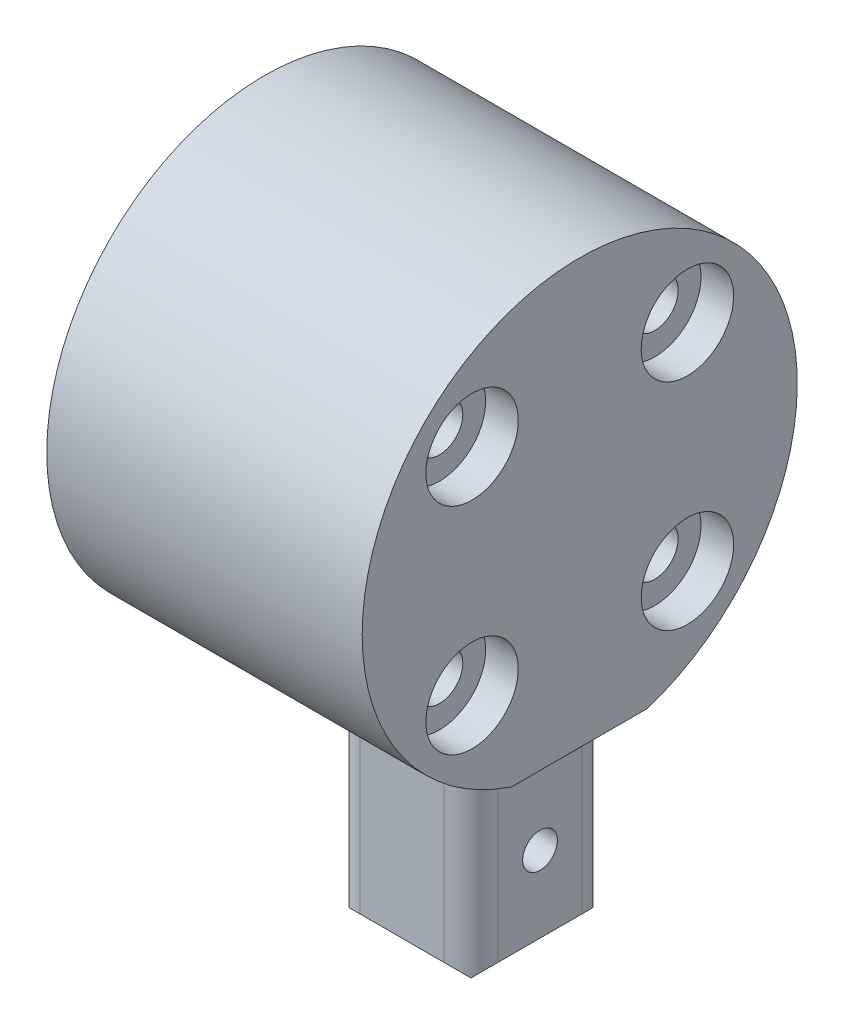
SolidWorks part; units mm, degrees
ref_plane "前视基准面" through (0, 0, 0) normal (0, 0, 1) x (1, 0, 0)
ref_plane "上视基准面" through (0, 0, 0) normal (0, 1, 0) x (1, 0, 0)
ref_plane "右视基准面" through (0, 0, 0) normal (1, 0, 0) x (0, 0, -1)
sketch "草图1" plane through (0, 0, 0) normal (1, 0, 0) x (0, 0, -1)
  circle A0 centre (0, 0) radius 20
  dimension "D1" = 40
extrude "凸台-拉伸1" add sketch "草图1" along normal blind 10
sketch "草图2" plane through (0, 0, 0) normal (-1, 0, 0) x (0, 0, 1)
  line L1 (-7.5, -15.25) -> (7.5, -15.25)
  line L2 (-7.5, -15.25) -> (-7.5, 15.25)
  line L3 (-7.5, 15.25) -> (7.5, 15.25)
  line L4 (7.5, -15.25) -> (7.5, 15.25)
  line L5 (-7.5, -15.25) -> (7.5, 15.25) construction
  line L6 (-7.5, 15.25) -> (7.5, -15.25) construction
  point P0 (0, 0)
  dimension "D1" = 15
  dimension "D2" = 30.5
extrude "切除-拉伸1" cut sketch "草图2" against normal blind 4
sketch "草图3" plane through (4, 0, 0) normal (-1, 0, 0) x (0, 0, 1)
  circle A0 centre (0, 0) radius 8.75
  dimension "D1" = 17.5
extrude "切除-拉伸2" cut sketch "草图3" along normal blind 4
sketch "草图4" plane through (0, 0, 0) normal (-1, 0, 0) x (0, 0, 1)
  line L1 (-9, -16) -> (9, -16)
  line L2 (-9, -16) -> (-9, 16)
  line L3 (-9, 16) -> (9, 16)
  line L4 (9, -16) -> (9, 16)
  line L5 (-9, -16) -> (9, 16) construction
  line L6 (-9, 16) -> (9, -16) construction
  circle A0 centre (0, 0) radius 20
  dimension "D3" = 40
  dimension "D1" = 32
  dimension "D2" = 18
extrude "凸台-拉伸2" add sketch "草图4" along normal blind 19
fillet "圆角1" radius 3 4 edges at (-9.5, -16, -9) (-9.5, -16, 9) (-9.5, 16, -9) (-9.5, 16, 9)
sketch "草图5" plane through (-19, 0, 0) normal (-1, 0, 0) x (0, 0, 1)
  line L0 (-6, -16) -> (6, -16) construction
  line L1 (6, 16) -> (-6, 16) construction
  circle A0 centre (0, -16) radius 2.5
  circle A1 centre (0, 16) radius 2.5
  dimension "D1" = 5
  dimension "D2" = 5
extrude "切除-拉伸3" cut sketch "草图5" against normal blind 20
fillet "圆角2" radius 3 4 edges at (-9.5, -16, -2.5) (-9.5, -16, 2.5) (-9.5, 16, -2.5) (-9.5, 16, 2.5)
sketch "草图6" plane through (10, 0, 0) normal (1, 0, 0) x (0, 0, -1)
  line L0 (0, 0) -> (20, 0) construction
  line L1 (0, 0) -> (18.216, -18.216) construction
  circle A0 centre (0, 0) radius 14 construction
  circle A2 centre (9.8995, -9.8995) radius 2.15
  circle A3 centre (0, 0) radius 14 construction
  circle A4 centre (-9.8995, -9.8995) radius 2.15
  circle A5 centre (0, 0) radius 14 construction
  circle A6 centre (-9.8995, 9.8995) radius 2.15
  circle A7 centre (0, 0) radius 14 construction
  circle A8 centre (9.8995, 9.8995) radius 2.15
  point P21 (0, 0)
  dimension "D1" = 28
  dimension "D3" = 4.3
  dimension "D2" = 45
  dimension "D4" = 4
extrude "切除-拉伸4" cut sketch "草图6" against normal blind 43
fillet "圆角3" radius 1 8 edges at (-9.5, -11.8523, 9) (-9.5, -7.9467, 9) (-9.5, -11.8523, -9) (-9.5, -7.9467, -9) (-9.5, 7.9467, -9) (-9.5, 11.8523, -9) (-9.5, 7.9467, 9) (-9.5, 11.8523, 9)
sketch "草图7" plane through (10, 0, 0) normal (1, 0, 0) x (0, 0, -1)
  circle A0 centre (9.8995, -9.8995) radius 4.25
  dimension "D1" = 8.5
extrude "切除-拉伸5" cut sketch "草图7" against normal blind 3
pattern_circular "阵列(圆周)1" count 4 over 360 about axis through (10, 0, 0) along (1, 0, 0) of "切除-拉伸5"
sketch "草图8" plane through (10, 0, 0) normal (1, 0, 0) x (0, 0, -1)
  line L1 (-11.4701, -19) -> (11.4701, -19)
  line L2 (-11.4701, -19) -> (-11.4701, -28.3124)
  line L3 (-11.4701, -28.3124) -> (11.4701, -28.3124)
  line L4 (11.4701, -19) -> (11.4701, -28.3124)
  line L5 (-11.4701, -19) -> (11.4701, -28.3124) construction
  line L6 (-11.4701, -28.3124) -> (11.4701, -19) construction
  point P0 (0, -23.6562)
  dimension "D1" = 19
extrude "切除-拉伸6" cut sketch "草图8" against normal blind 20
sketch "草图9" plane through (0, -19, 0) normal (0, -1, 0) x (1, 0, 0)
  line L1 (-3, -3) -> (3, -3)
  line L2 (-3, -3) -> (-3, 3)
  line L3 (-3, 3) -> (3, 3)
  line L4 (3, -3) -> (3, 3)
  line L5 (-3, -3) -> (3, 3) construction
  line L6 (-3, 3) -> (3, -3) construction
  point P0 (0, 0)
  dimension "D1" = 6
  dimension "D2" = 6
extrude "切除-拉伸7" cut sketch "草图9" against normal blind 4
sketch "草图10" plane through (0, -19, 0) normal (0, -1, 0) x (1, 0, 0)
  line L0 (10, -6.245) -> (10, 6.245) construction
  line L1 (-6.35, -6.35) -> (6.35, -6.35)
  line L2 (-6.35, -6.35) -> (-6.35, 6.35)
  line L3 (-6.35, 6.35) -> (6.35, 6.35)
  line L4 (6.35, -6.35) -> (6.35, 6.35)
  line L5 (-6.35, -6.35) -> (6.35, 6.35) construction
  line L6 (-6.35, 6.35) -> (6.35, -6.35) construction
  line L7 (-3, -3) -> (3, -3)
  line L8 (-3, -3) -> (-3, 3)
  line L9 (-3, 3) -> (3, 3)
  line L10 (3, -3) -> (3, 3)
  line L11 (-3, -3) -> (3, 3) construction
  line L12 (-3, 3) -> (3, -3) construction
  point P0 (0, 0)
  point P6 (0, 0)
  dimension "D1" = 12.7
  dimension "D2" = 12.7
  dimension "D3" = 10
extrude "凸台-拉伸3" add sketch "草图10" along normal blind 20 and the other way blind 0.5
sketch "草图11" plane through (-6.35, 0, 0) normal (-1, 0, 0) x (0, 0, 1)
  line L0 (-6.245, -19) -> (6.245, -19) construction
  line L1 (6.35, -18.9652) -> (6.35, -39) construction
  line L2 (-6.35, -18.9652) -> (-6.35, -39) construction
  circle A0 centre (0, -29) radius 1.6
  dimension "D1" = 3.2
  dimension "D2" = 10
  dimension "D3" = 6.35
  dimension "D4" = 6.35
extrude "切除-拉伸8" cut sketch "草图11" against normal blind 20
chamfer "倒角1" distance 3 angle 45 2 edges at (-3, -27.7342, -3) (-3, -27.7342, 3)
fillet "圆角4" radius 2 4 edges at (-0.5003, -16.8675, 2.4997) (-0.5003, -16.8675, -2.4997) (-1.8082, -18.1976, 1.1918) (-1.8082, -18.1976, -1.1918)
chamfer "倒角2" distance 3 angle 45 4 edges at (6.35, -39, 0) (0, -39, -6.35) (-6.35, -39, 0) (0, -39, 6.35)
sketch "草图13" plane through (0, -39, 0) normal (0, -1, 0) x (1, 0, 0)
  line L0 (10, -6.245) -> (10, 6.245) construction
  circle A0 centre (0, 0) radius 3.35
  dimension "D1" = 6.7
fillet "圆角5" radius 2.5 4 edges at (6.35, -27.4826, -6.35) (6.35, -27.4826, 6.35) (-6.35, -27.4826, 6.35) (-6.35, -27.4826, -6.35)
